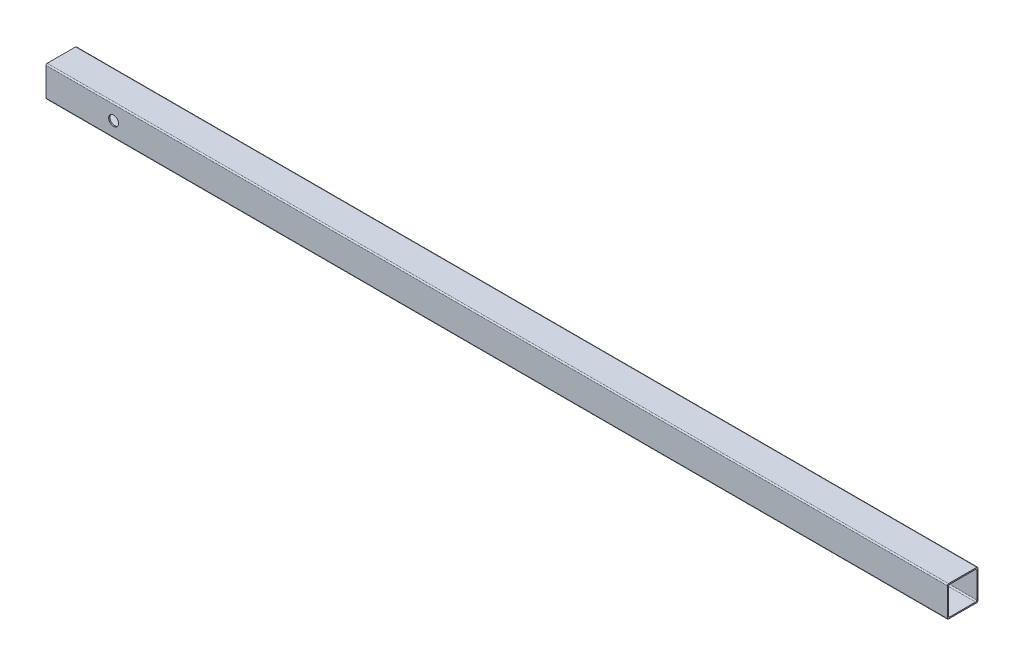
SolidWorks part; units mm, degrees
material "Thornel Mat VMA"
ref_plane "Front Plane" through (0, 0, 0) normal (0, 0, 1) x (1, 0, 0)
ref_plane "Top Plane" through (0, 0, 0) normal (0, 1, 0) x (1, 0, 0)
ref_plane "Right Plane" through (0, 0, 0) normal (1, 0, 0) x (0, 0, -1)
sketch "Sketch2" plane through (0, 0, 0) normal (1, 0, 0) x (0, 0, -1)
  line L1 (0.762, 0) -> (18.288, 0)
  line L2 (0, 0.762) -> (0, 18.288)
  line L3 (0.762, 19.05) -> (18.288, 19.05)
  line L4 (19.05, 0.762) -> (19.05, 18.288)
  line L5 (1.524, 0.762) -> (17.526, 0.762)
  line L6 (0.762, 1.524) -> (0.762, 17.526)
  line L7 (1.524, 18.288) -> (17.526, 18.288)
  line L8 (18.288, 1.524) -> (18.288, 17.526)
  arc A0 (17.526, 18.288) -> (18.288, 17.526) centre (17.526, 17.526) cw
  arc A1 (17.526, 0.762) -> (18.288, 1.524) centre (17.526, 1.524) ccw
  arc A2 (1.524, 0.762) -> (0.762, 1.524) centre (1.524, 1.524) cw
  arc A3 (0.762, 17.526) -> (1.524, 18.288) centre (1.524, 17.526) cw
  arc A4 (18.288, 19.05) -> (19.05, 18.288) centre (18.288, 18.288) cw
  arc A5 (18.288, 0) -> (19.05, 0.762) centre (18.288, 0.762) ccw
  arc A6 (0.762, 0) -> (0, 0.762) centre (0.762, 0.762) cw
  arc A7 (0, 18.288) -> (0.762, 19.05) centre (0.762, 18.288) cw
  point P11 (18.288, 18.288)
  point P14 (18.288, 0.762)
  point P19 (0.762, 18.288)
  point P22 (19.05, 19.05)
  point P25 (19.05, 0)
  point P28 (0, 0)
  point P31 (0, 19.05)
  dimension "D7" = 0.762
  dimension "D1" = 19.05
  dimension "D2" = 19.05
  dimension "D5" = 0.762
  dimension "D6" = 0.762
  dimension "D3" = 0.762
  dimension "D4" = 0.762
extrude "Boss-Extrude1" add sketch "Sketch2" along normal blind 558.8
sketch "Sketch3" plane through (0, 0, 0) normal (0, 0, 1) x (1, 0, 0)
  line L0 (0, 18.288) -> (0, 0.762) construction
  line L1 (558.8, 19.05) -> (0, 19.05) construction
  circle A0 centre (41.91, 9.525) radius 3.048
  dimension "D1" = 6.096
  dimension "D2" = 41.91
  dimension "D3" = 9.525
extrude "Cut-Extrude1" cut sketch "Sketch3" against normal up to surface (19.05 mm away) up to face at (279.4, 9.525, -19.05)
sketch "Sketch4" plane through (558.8, 0, 0) normal (1, 0, 0) x (0, 0, -1)
  line L1 (0, 12.573) -> (0, 6.477)
  line L2 (0, 12.573) -> (0, 6.477)
  line L6 (19.05, 0.762) -> (19.05, 18.288)
  line L7 (0.762, 0) -> (18.288, 0)
  line L8 (0, 18.288) -> (0, 0.762)
  line L9 (18.288, 19.05) -> (0.762, 19.05)
  line L10 (19.05, 0.762) -> (19.05, 18.288)
  line L11 (0.762, 0) -> (18.288, 0)
  line L12 (0, 18.288) -> (0, 0.762)
  line L13 (18.288, 19.05) -> (0.762, 19.05)
  arc A4 (19.05, 18.288) -> (18.288, 19.05) centre (18.288, 18.288) ccw
  arc A5 (18.288, 0) -> (19.05, 0.762) centre (18.288, 0.762) ccw
  arc A6 (0, 0.762) -> (0.762, 0) centre (0.762, 0.762) ccw
  arc A7 (0.762, 19.05) -> (0, 18.288) centre (0.762, 18.288) ccw
  arc A8 (19.05, 18.288) -> (18.288, 19.05) centre (18.288, 18.288) ccw
  arc A9 (18.288, 0) -> (19.05, 0.762) centre (18.288, 0.762) ccw
  arc A10 (0, 0.762) -> (0.762, 0) centre (0.762, 0.762) ccw
  arc A11 (0.762, 19.05) -> (0, 18.288) centre (0.762, 18.288) ccw
  dimension "D1" = 0
  dimension "D2" = 0
equation "\"shaft\"=0.75"
equation "\"D1@Sketch2\"=\"shaft\""
equation "\"D2@Sketch2\"=\"shaft\""
equation "\"IDshaft\"=0.4375"
equation "\"D3@Sketch3\"=\"shaft\"/2"
